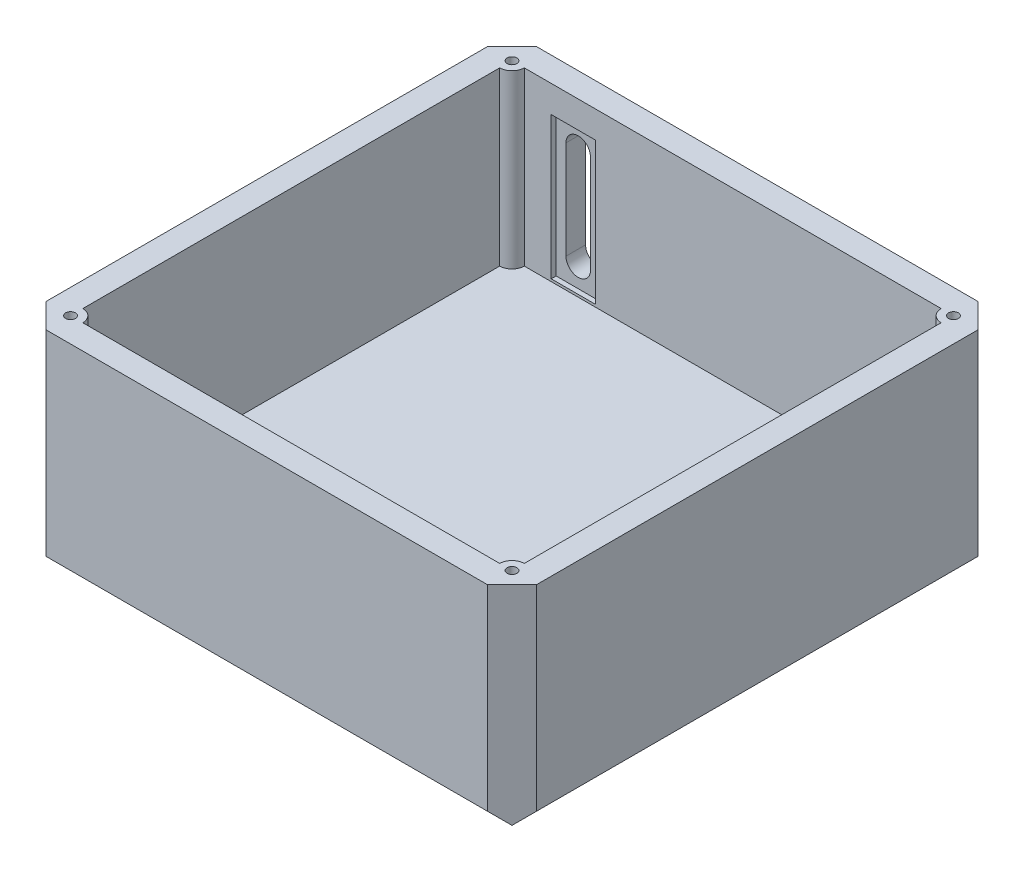
SolidWorks part; units mm, degrees
ref_plane "Front Plane" through (0, 0, 0) normal (0, 0, 1) x (1, 0, 0)
ref_plane "Top Plane" through (0, 0, 0) normal (0, 1, 0) x (1, 0, 0)
ref_plane "Right Plane" through (0, 0, 0) normal (1, 0, 0) x (0, 0, -1)
sketch "Sketch1" plane through (0, 0, 0) normal (0, 1, 0) x (1, 0, 0)
  line L1 (100, -100) -> (-100, -100)
  line L2 (100, -100) -> (100, 100)
  line L3 (100, 100) -> (-100, 100)
  line L4 (-100, -100) -> (-100, 100)
  line L5 (100, -100) -> (-100, 100) construction
  line L6 (100, 100) -> (-100, -100) construction
  point P0 (0, 0)
  dimension "D1" = 200
  dimension "D2" = 200
extrude "Boss-Extrude1" add sketch "Sketch1" along normal blind 100
chamfer "Chamfer1" distance 20 angle 45 4 edges at (100, 0, 0) (0, 0, -100) (-100, 0, 0) (0, 0, 100)
sketch "Sketch2" plane through (0, 100, 0) normal (0, 1, 0) x (1, 0, 0)
  line L0 (0, 0) -> (-179.5549, 0) construction
  line L1 (0, 0) -> (0, 117.1127) construction
  line L2 (-100, 100) -> (-100, -100) construction
  line L3 (100, 100) -> (-100, 100) construction
  line L4 (-84, 90) -> (84, 90)
  line L5 (90, 85) -> (90, -85)
  line L6 (84, -90) -> (-84, -90)
  line L7 (-90, 85) -> (-90, -85)
  line L8 (84, 90) -> (85, 90)
  line L9 (-84, 90) -> (-85, 90)
  line L10 (-84, -90) -> (-85, -90)
  line L11 (84, -90) -> (85, -90)
  circle A0 centre (-90, 90) radius 2
  circle A1 centre (90, 90) radius 2
  circle A2 centre (90, -90) radius 2
  circle A3 centre (-90, -90) radius 2
  circle A4 centre (-90, 90) radius 5
  circle A5 centre (90, 90) radius 5
  circle A6 centre (90, -90) radius 5
  circle A7 centre (-90, -90) radius 5
  dimension "D1" = 4
  dimension "D2" = 10
  dimension "D3" = 10
  dimension "D4" = 3
extrude "Cut-Extrude3" cut sketch "Sketch2" against normal blind 70 contours L7 A7 L6 A6 L5 A5 L4 A4 region at (0, 100, 0)
sketch "Sketch6" plane through (0, 100, 0) normal (0, 1, 0) x (1, 0, 0)
extrude "Cut-Extrude4" cut sketch "Sketch2<7>" against normal through all contours A2 | A3 | A0 | A1 region at (90, 100, 90)
sketch "Sketch2<7>" plane through (0, 100, 0) normal (0, 1, 0) x (1, 0, 0) same geometry as "Sketch2"
sketch "Sketch7" plane through (0, 0, -100) normal (0, 0, -1) x (-1, 0, 0)
  line L0 (65, 80) -> (65, 40) construction
  line L1 (70, 80) -> (70, 40)
  line L2 (60, 80) -> (60, 40)
  line L3 (100, 100) -> (100, 20) construction
  line L4 (100, 60) -> (60, 60) construction
  arc A0 (70, 80) -> (60, 80) centre (65, 80) ccw
  arc A1 (60, 40) -> (70, 40) centre (65, 40) ccw
  point P2 (65, 60)
  dimension "D2" = 5
  dimension "D3" = 40
  dimension "D1" = 30
extrude "Cut-Extrude7" cut sketch "Sketch7" against normal up to surface (10 mm away) up to face at (0, 65, -90)
sketch "Sketch9" plane through (0, 0, -90) normal (0, 0, 1) x (1, 0, 0)
  line L0 (-60, 60) -> (-56, 60) construction
  line L1 (-74, 89) -> (-56, 89)
  line L2 (-74, 89) -> (-74, 31)
  line L3 (-74, 31) -> (-56, 31)
  line L4 (-56, 89) -> (-56, 31)
  line L5 (-60, 80) -> (-60, 40) construction
  line L6 (-65, 35) -> (-65, 31) construction
  arc A0 (-70, 40) -> (-60, 40) centre (-65, 40) ccw construction
  dimension "D1" = 4
  dimension "D2" = 4
extrude "Cut-Extrude8" cut sketch "Sketch9" against normal blind 2
extrude "Cut-Extrude9" cut sketch "Sketch2<8>" against normal through all from offset 80 contours A5 A1 | A6 A2 | A7 A3 | A4 A0 region at (-86.5645, 100, -86.5645) region at (90, 100, -94.8586) region at (-86.5645, 100, 86.5645) region at (93.4355, 100, 86.5645) offset against normal yes
sketch "Sketch2<8>" plane through (0, 100, 0) normal (0, 1, 0) x (1, 0, 0) same geometry as "Sketch2"
chamfer "Chamfer2" distance 10 angle 45 4 edges at (100, 60, 100) (-100, 60, 100) (-100, 60, -100) (100, 60, -100)
